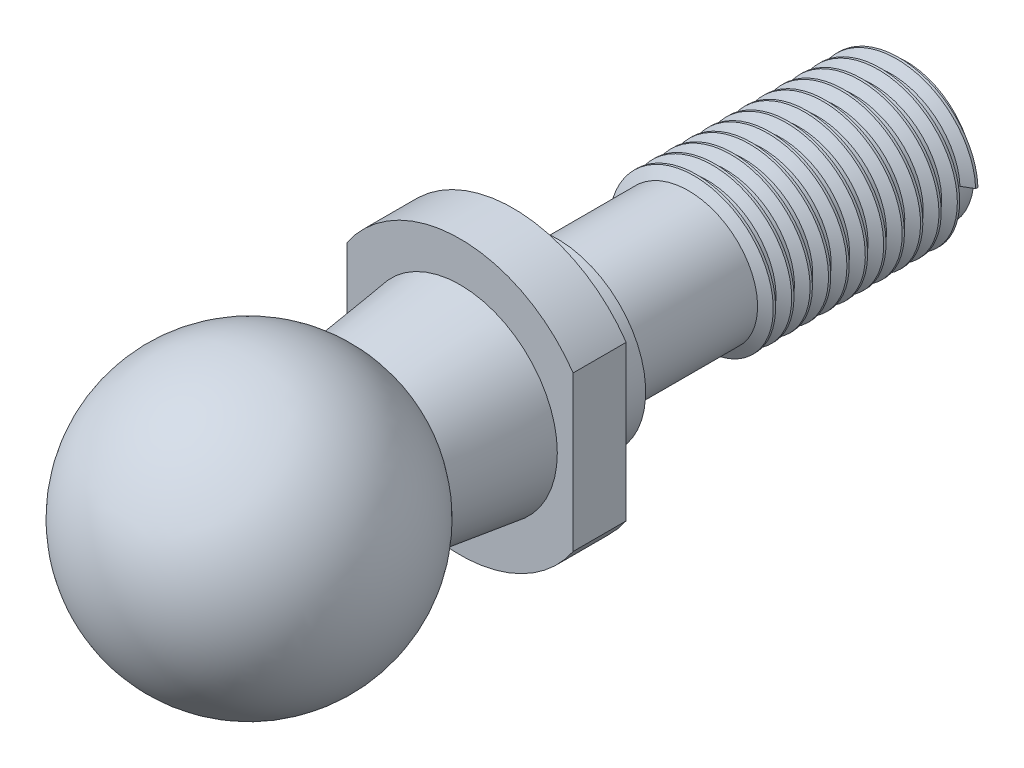
SolidWorks part; units mm, degrees
ref_plane "Front Plane" through (0, 0, 0) normal (0, 0, 1) x (1, 0, 0)
ref_plane "Top Plane" through (0, 0, 0) normal (0, 1, 0) x (1, 0, 0)
ref_plane "Right Plane" through (0, 0, 0) normal (1, 0, 0) x (0, 0, -1)
sketch "Sketch1" plane through (0, 0, 0) normal (1, 0, 0) x (0, 0, -1)
  line L0 (0, 8.255) -> (0, -8.255)
  arc A0 (0, 8.255) -> (0, -8.255) centre (0, 0) ccw
  dimension "D1" = 16.51
revolve "Revolve1" add sketch "Sketch1" angle 360 about L0
sketch "Sketch2" plane through (0, 0, 0) normal (1, 0, 0) x (0, 0, -1)
  line L0 (6.6564, 4.8824) -> (6.6564, 0)
  line L1 (6.6564, 0) -> (12.1382, 0)
  line L2 (12.1382, 0) -> (12.1382, 5.588)
  line L3 (12.1382, 5.588) -> (6.6564, 4.8824)
  circle A0 centre (0, 0) radius 8.255 construction
  point P4 (0, 0)
  dimension "D1" = 4.8824
  dimension "D2" = 5.588
  dimension "D3" = 5.4818
revolve "Revolve3" add sketch "Sketch2" angle 360 about L1
sketch "Sketch3" plane through (0, 0, -12.1382) normal (0, 0, -1) x (-1, 0, 0)
  line L0 (-6.4994, 4.445) -> (-6.4994, -4.445)
  line L1 (6.4994, 4.445) -> (6.4994, -4.445)
  arc A0 (-6.4994, -4.445) -> (6.4994, -4.445) centre (0, 0) ccw
  arc A1 (6.4994, 4.445) -> (-6.4994, 4.445) centre (0, 0) ccw
  dimension "D1" = 15.748
  dimension "D2" = 8.89
  dimension "D3" = 8.89
extrude "Boss-Extrude1" add sketch "Sketch3" along normal blind 3.048
sketch "Sketch4" plane through (0, 0, -15.1862) normal (0, 0, -1) x (-1, 0, 0)
  circle A0 centre (0, 0) radius 5.08
  dimension "D1" = 10.16
extrude "Boss-Extrude2" add sketch "Sketch4" along normal blind 2.54
sketch "Sketch5" plane through (0, 0, -17.7262) normal (0, 0, -1) x (-1, 0, 0)
  circle A0 centre (0, 0) radius 3.8796
  dimension "D1" = 7.7591
extrude "Boss-Extrude3" add sketch "Sketch5" along normal blind 20.066
thread "Thread1" pitch 1.0583 method extrude profile "Thread Profile1" start angle 0, offset 0, length 12.446, pitch 1.0583, diameter 7.7591
ref_plane "Plane1" through (3.8796, 0, -37.7922) normal (0, -1, 0) x (1, 0, 0)
sketch "Thread Profile1" plane through (3.8796, 0, -37.7922) normal (0, -1, 0) x (1, 0, 0)
  line L0 (0, 0) -> (0, 1.0583) construction
  line L1 (0, 0) -> (0.5728, 0.3307)
  line L2 (0.5728, 0.3307) -> (0.5728, 0.463)
  line L3 (0.5728, 0.463) -> (0, 0.7937)
  line L4 (0.5728, 0.3969) -> (0, 0.3969) construction
  line L11 (0, 0) -> (0, 0.7937)
  point P2 (0, 0)
  dimension "Pitch" = 1.0583
  dimension "Profile_Angle" = 60
  dimension "Profile_Land" = 0.1323
  dimension "Profile_Height" = 0.5728
